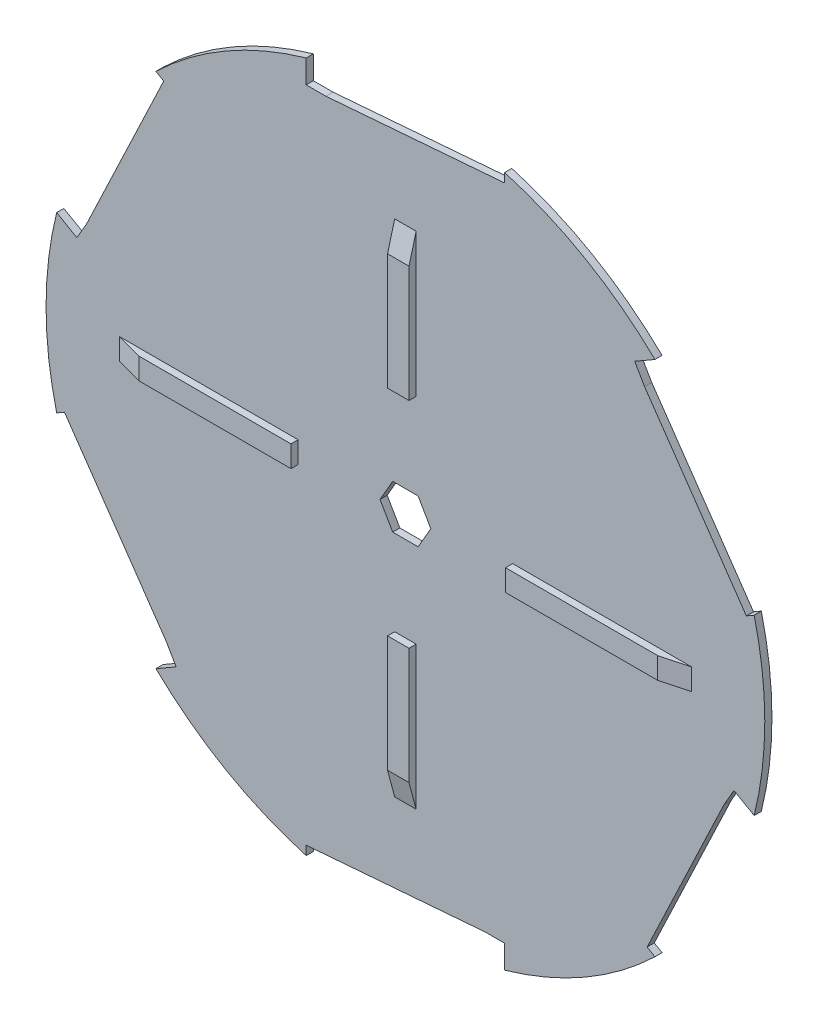
SolidWorks part; units mm, degrees
ref_plane "Front Plane" through (0, 0, 0) normal (0, 0, 1) x (1, 0, 0)
ref_plane "Top Plane" through (0, 0, 0) normal (0, 1, 0) x (1, 0, 0)
ref_plane "Right Plane" through (0, 0, 0) normal (1, 0, 0) x (0, 0, -1)
sketch "Sketch1" plane through (0, 0, 0) normal (0, 0, 1) x (1, 0, 0)
  circle A0 centre (0, 0) radius 100.5
  dimension "D1" = 201
extrude "Boss-Extrude1" add sketch "Sketch1" along normal blind 2 contours A0
sketch "Sketch8" plane through (0, 0, 0) normal (0, 0, -1) x (-1, 0, 0)
  text T0 "02-04-141118"
extrude "Cut-Extrude6" cut sketch "Sketch8" against normal blind 0.2
sketch "Sketch9" plane through (0, 0, 2) normal (0, 0, 1) x (1, 0, 0)
  line L1 (-7.1014, 0) -> (-3.5507, -6.15)
  line L2 (-3.5507, -6.15) -> (3.5507, -6.15)
  line L3 (3.5507, -6.15) -> (7.1014, 0)
  line L4 (7.1014, 0) -> (3.5507, 6.15)
  line L5 (3.5507, 6.15) -> (-3.5507, 6.15)
  line L6 (-3.5507, 6.15) -> (-7.1014, 0)
  circle A0 centre (0, 0) radius 6.15 construction
  dimension "D1" = 12.3
extrude "Cut-Extrude7" cut sketch "Sketch9" against normal blind 10
sketch "Sketch11" plane through (0, 0, 2) normal (0, 0, 1) x (1, 0, 0)
  line L0 (0, 0) -> (-80, 0)
  line L1 (-80, 0) -> (-80, 3)
  line L2 (-80, 3) -> (-30, 3)
  line L3 (-30, 3) -> (-30, -3)
  line L4 (-30, -3) -> (-80, -3)
  line L5 (-80, -3) -> (-80, 0)
  line L6 (0, 0) -> (0, 70)
  line L7 (0, 70) -> (-3, 70)
  line L8 (-3, 70) -> (-3, 30)
  line L9 (-3, 30) -> (3, 30)
  line L10 (3, 30) -> (3, 70)
  line L11 (3, 70) -> (0, 70)
  line L12 (30, 3) -> (80, 3)
  line L13 (30, -3) -> (30, 3)
  line L14 (80, -3) -> (30, -3)
  line L15 (80, 3) -> (80, 0)
  line L16 (80, 0) -> (80, -3)
  line L17 (3, -30) -> (-3, -30)
  line L18 (3, -70) -> (3, -30)
  line L19 (-3, -30) -> (-3, -70)
  line L20 (0, -70) -> (3, -70)
  line L21 (-3, -70) -> (0, -70)
  point P20 (0, 0)
  point P26 (0, 0)
  dimension "D1" = 3
  dimension "D2" = 6
  dimension "D3" = 6
  dimension "D4" = 3
  dimension "D5" = 80
  dimension "D6" = 50
  dimension "D7" = 70
  dimension "D8" = 40
  dimension "D9" = 2
  dimension "D10" = 2
extrude "Boss-Extrude2" add sketch "Sketch11" along normal blind 2 contours L7 L8 L9 L10 L11 | L1 L2 L3 L4 L5 | L14 L13 L12 L15 L16 | L19 L21 L20 L18 L17
chamfer "Chamfer1" distance 2 angle 75 4 edges at (80, 0, 4) (0, 70, 4) (0, -70, 4) (-80, 0, 4)
sketch "Sketch13" plane through (0, 0, 2) normal (0, 0, 1) x (1, 0, 0)
  line L1 (-27.75, 96.0726) -> (-27.75, 103.1157)
  line L2 (27.75, 94.0726) -> (27.75, 96.0726)
  line L3 (-22.25, 90.0726) -> (-27.75, 90.0726)
  line L4 (-27.75, 90.0726) -> (-27.75, 96.0726)
  line L6 (-22.25, 90.0726) -> (27.75, 94.0726)
  line L7 (-27.75, 103.1157) -> (27.75, 103.1157)
  line L8 (27.75, 103.1157) -> (27.75, 96.0726)
  line L10 (64.1301, 69.0685) -> (69.3263, 72.0685)
  line L11 (66.8801, 64.3053) -> (64.1301, 69.0685)
  line L12 (69.3263, 72.0685) -> (75.4258, 75.5901)
  line L13 (75.4258, 75.5901) -> (103.1758, 27.5257)
  line L14 (103.1758, 27.5257) -> (97.0763, 24.0041)
  line L15 (95.3442, 23.0041) -> (97.0763, 24.0041)
  line L16 (66.8801, 64.3053) -> (95.3442, 23.0041)
  line L17 (91.8801, -21.0041) -> (97.0763, -24.0041)
  line L18 (89.1301, -25.7672) -> (91.8801, -21.0041)
  line L19 (97.0763, -24.0041) -> (103.1758, -27.5257)
  line L20 (103.1758, -27.5257) -> (75.4258, -75.5901)
  line L21 (75.4258, -75.5901) -> (69.3263, -72.0685)
  line L22 (67.5942, -71.0685) -> (69.3263, -72.0685)
  line L23 (89.1301, -25.7672) -> (67.5942, -71.0685)
  line L24 (27.75, -90.0726) -> (27.75, -96.0726)
  line L25 (22.25, -90.0726) -> (27.75, -90.0726)
  line L26 (27.75, -96.0726) -> (27.75, -103.1157)
  line L27 (27.75, -103.1157) -> (-27.75, -103.1157)
  line L28 (-27.75, -103.1157) -> (-27.75, -96.0726)
  line L29 (-27.75, -94.0726) -> (-27.75, -96.0726)
  line L30 (22.25, -90.0726) -> (-27.75, -94.0726)
  line L31 (-64.1301, -69.0685) -> (-69.3263, -72.0685)
  line L32 (-66.8801, -64.3053) -> (-64.1301, -69.0685)
  line L33 (-69.3263, -72.0685) -> (-75.4258, -75.5901)
  line L34 (-75.4258, -75.5901) -> (-103.1758, -27.5257)
  line L35 (-103.1758, -27.5257) -> (-97.0763, -24.0041)
  line L36 (-95.3442, -23.0041) -> (-97.0763, -24.0041)
  line L37 (-66.8801, -64.3053) -> (-95.3442, -23.0041)
  line L38 (-91.8801, 21.0041) -> (-97.0763, 24.0041)
  line L39 (-89.1301, 25.7672) -> (-91.8801, 21.0041)
  line L40 (-97.0763, 24.0041) -> (-103.1758, 27.5257)
  line L41 (-103.1758, 27.5257) -> (-75.4258, 75.5901)
  line L42 (-75.4258, 75.5901) -> (-69.3263, 72.0685)
  line L43 (-67.5942, 71.0685) -> (-69.3263, 72.0685)
  line L44 (-89.1301, 25.7672) -> (-67.5942, 71.0685)
  point P48 (0, 0)
  dimension "D1" = 6
  dimension "D4" = 2
  dimension "D5" = 6
  dimension "D6" = 5.5
extrude "Cut-Extrude9" cut sketch "Sketch13" against normal blind 10
equation "\"1.5.00mm\"=3"
